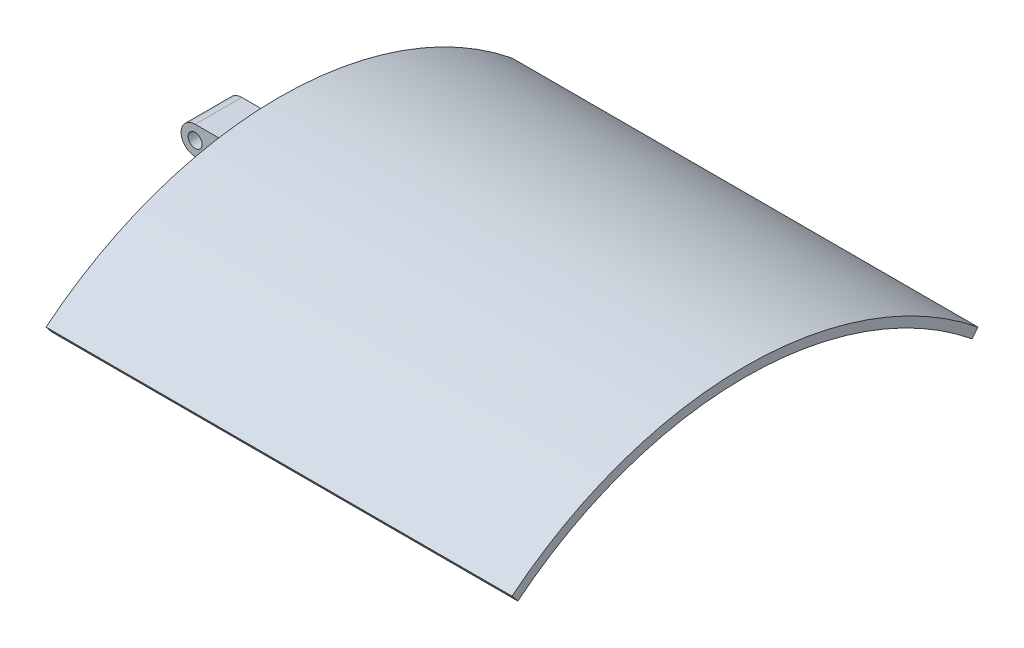
SolidWorks part; units mm, degrees
ref_plane "Plan de face" through (0, 0, 0) normal (0, 0, 1) x (1, 0, 0)
ref_plane "Plan de dessus" through (0, 0, 0) normal (0, 1, 0) x (1, 0, 0)
ref_plane "Plan de droite" through (0, 0, 0) normal (1, 0, 0) x (0, 0, -1)
sketch "Esquisse1" plane through (0, 0, 0) normal (1, 0, 0) x (0, 0, -1)
  line L0 (-50, 61.8082) -> (0, 0) construction
  line L1 (0, 0) -> (50, 61.8082) construction
  line L2 (-50, 61.8082) -> (50, 61.8082) construction
  line L3 (0, 61.8082) -> (0, 0) construction
  line L4 (-50, 61.8082) -> (-48.7421, 60.2532)
  line L5 (50, 61.8082) -> (48.7421, 60.2532)
  arc A0 (-50, 61.8082) -> (50, 61.8082) centre (0, 0) cw
  arc A1 (-48.7421, 60.2532) -> (48.7421, 60.2532) centre (0, 0) cw
  dimension "D1" = 77.5
  dimension "D2" = 77.943
  dimension "D3" = 2
  dimension "D4" = 100
extrude "Boss.-Extru.1" add sketch "Esquisse1" along normal blind 100
sketch "Esquisse7" plane through (0, 0, 0) normal (0, 0, 1) x (1, 0, 0)
  line L0 (7, 77.5) -> (7, 70.5)
  line L1 (100, 77.5) -> (0, 77.5) construction
  line L2 (7, 77.5) -> (13, 77.5)
  line L3 (13, 77.5) -> (13, 64.5)
  line L5 (13, 64.5) -> (-13, 64.5)
  line L6 (-13, 64.5) -> (-13, 70.5) construction
  line L7 (-13, 70.5) -> (7, 70.5)
  line L10 (10, 77.5) -> (0, 77.5) construction
  line L11 (-13, 67.5) -> (7, 67.5) construction
  line L12 (7, 67.5) -> (7, 70.5) construction
  line L13 (7, 67.5) -> (7, 64.5) construction
  line L14 (7, 70.5) -> (-1.6824, 119.7404) construction
  circle A0 centre (-13, 67.5) radius 1.5
  arc A1 (-13, 70.5) -> (-13, 64.5) centre (-13, 67.5) ccw
  dimension "D3" = 3
  dimension "D1" = 6
  dimension "D2" = 10
  dimension "D4" = 23
  dimension "D5" = 10
  dimension "D6" = 80
  dimension "D7" = 50
extrude "Boss.-Extru.3" add sketch "Esquisse7" along normal blind 5 and the other way blind 5 contours L7 L0 L2 L3 L5 A1 | A0
sketch "Esquisse3" plane through (0, 0, 0) normal (0, 0, 1) x (1, 0, 0)
  line L0 (30.7214, 77.5) -> (30.7214, 72.5)
  line L1 (100, 77.5) -> (13, 77.5) construction
  line L2 (30.7214, 72.5) -> (36.7214, 72.5) construction
  line L3 (36.7214, 72.5) -> (36.7214, 77.5)
  line L4 (36.7214, 77.5) -> (30.7214, 77.5)
  line L5 (-74.1468, 29.3655) -> (-127.2256, 20.0063) construction
  line L6 (-73.1207, 23.5464) -> (-132.9596, 12.9952) construction
  line L7 (-11, 40.5) -> (-11, 34.5) construction
  line L8 (-13, 67.5) -> (-11, 67.5) construction
  line L9 (36.7214, -12.0757) -> (36.7214, -21.0592) construction
  line L10 (30.7214, 72.5) -> (36.7214, 72.5) construction
  line L11 (30.7214, -123.9412) -> (30.7214, -122.8027) construction
  line L12 (72.7696, 84.9142) -> (60.2573, 82.708) construction
  line L13 (132.8929, 62.8722) -> (91.2136, 55.523) construction
  line L14 (123.3905, 91.5493) -> (80.4346, 83.975) construction
  line L15 (-13, 67.5) -> (-7.8094, 38.0626) construction
  line L16 (-11, 37.5) -> (-16.5823, 69.1591) construction
  line L17 (-13, 67.5) -> (-11, 37.5) construction
  line L18 (-11, 37.5) -> (33.7214, 77.5) construction
  line L19 (33.7214, 77.5) -> (-13, 67.5) construction
  line L20 (30.7214, 77.5) -> (-13, 77.5) construction
  line L21 (-13, 77.5) -> (-13, 67.5) construction
  line L22 (-11, 67.5) -> (-11, 37.5) construction
  arc A0 (-11, 40.5) -> (-11, 34.5) centre (-11, 37.5) ccw
  circle A1 centre (-11, 37.5) radius 1.5
  arc A2 (-11, 34.5) -> (36.7214, 72.5) centre (-2.2688, 72.5) ccw construction
  arc A3 (-11, 40.5) -> (30.7214, 72.5) centre (-2.4112, 72.5) ccw construction
  spline S0 degree 3 poles (30.7214, 72.5) (30.7214, 44.695) (24.9104, 46.832) (-11, 40.5) knots 0 0 0 0 1 1 1 1
  spline S1 degree 3 poles (36.7214, 72.5) (36.7214, 41.4065) (28.3973, 41.4468) (-11, 34.5) knots 0 0 0 0 1 1 1 1
  text T0 "A"
  text T1 "C"
  text T2 "B"
  text T3 "B'"
  point P27 (-13, 67.5)
  dimension "D4" = 3
  dimension "D5" = 12.081
  dimension "D2" = 5
  dimension "D3" = 6
  dimension "D6" = 10
  dimension "D7" = 3.2398
  dimension "D8" = 60
  dimension "D9" = 2
  dimension "D10" = 30.0666
  dimension "D11" = 40
  dimension "D12" = 47.7796
extrude "Boss.-Extru.2" add sketch "Esquisse3" along normal blind 3 and the other way blind 3 contours L3 L4 L0 S0 A0 S1 | A1
ref_plane "Plan2" through (0, 67.5, 0) normal (0, 1, 0) x (1, 0, 0)
ref_plane "Plan3" through (0, 0, 0) normal (0, 0, 1) x (1, 0, 0)
ref_plane "Plan4" through (0, 79.5, 0) normal (0, 1, 0) x (1, 0, 0)
sketch "Esquisse8" plane through (0, 79.5, 0) normal (0, 1, 0) x (1, 0, 0)
  line L0 (30.7214, -3) -> (36.7214, -3) construction
  line L1 (30.7214, 3) -> (30.7214, -3) construction
  line L2 (30.7214, 3) -> (36.7214, 3) construction
  line L3 (30.7214, -3) -> (36.7214, -3) construction
  line L4 (30.7214, 3) -> (30.7214, -3) construction
  line L5 (30.7214, 3) -> (36.7214, 3) construction
  line L6 (36.7214, -3) -> (36.7214, 3) construction
  line L7 (36.7214, -3) -> (36.7214, 3) construction
  line L8 (30.7214, -3) -> (36.7214, 3) construction
  line L9 (30.7214, 3) -> (36.7214, -3) construction
  point P3 (33.7214, 0)
sketch "Esquisse9" plane through (0, 0, 0) normal (0, 0, 1) x (1, 0, 0)
  line L0 (-11, 37.5) -> (-13, 67.5) construction
  line L1 (-13, 67.5) -> (33.7214, 79.5) construction
  line L2 (33.7214, 79.5) -> (-11, 37.5) construction
  line L3 (100, 79.5) -> (0, 79.5) construction
  line L4 (100, 79.5) -> (0, 79.5) construction
  line L5 (-13, 67.5) -> (-13, 79.5) construction
  line L6 (-13, 79.5) -> (0, 79.5) construction
  point P0 (-13, 67.5)
  point P1 (-11, 37.5)
  dimension "D1" = 50.611
  dimension "D2" = 28.798
  dimension "D3" = 100.591
  dimension "D4" = 14.405
